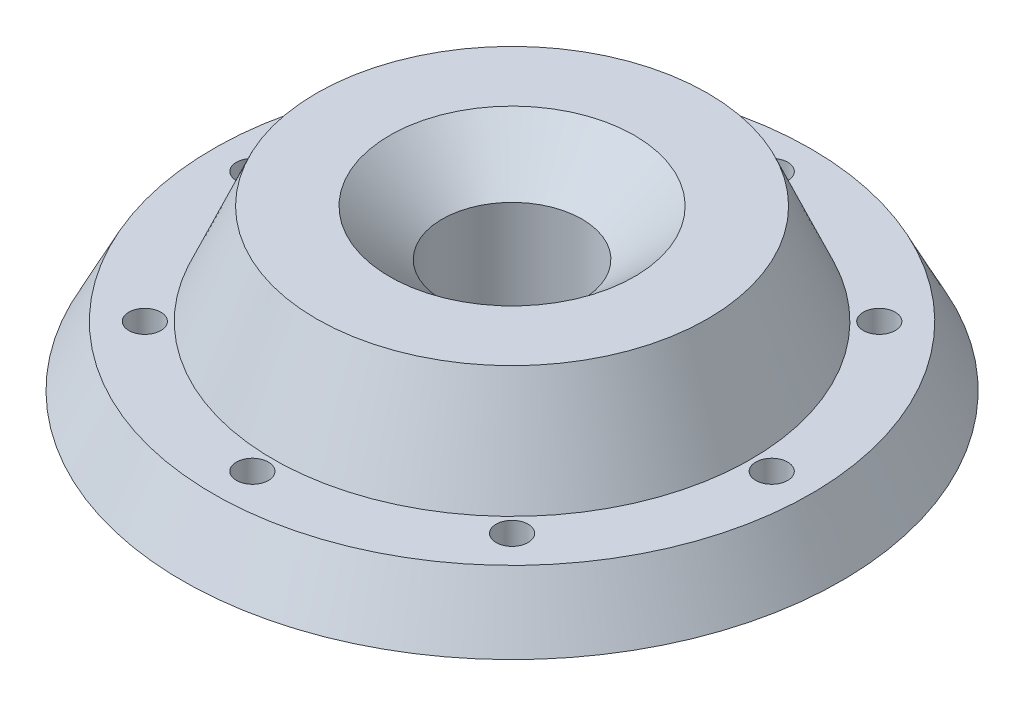
SolidWorks part; units mm, degrees
ref_plane "Front Plane" through (0, 0, 0) normal (0, 0, 1) x (1, 0, 0)
ref_plane "Top Plane" through (0, 0, 0) normal (0, 1, 0) x (1, 0, 0)
ref_plane "Right Plane" through (0, 0, 0) normal (1, 0, 0) x (0, 0, -1)
sketch "Sketch1" plane through (0, 0, 0) normal (0, 1, 0) x (1, 0, 0)
  circle A0 centre (0, 0) radius 56 construction
  circle A1 centre (0, 0) radius 82.5 construction
  circle A2 centre (65, 0) radius 4 construction
  circle A3 centre (65, 0) radius 4
  circle A4 centre (45.9619, -45.9619) radius 4 construction
  circle A5 centre (0, -65) radius 4 construction
  circle A6 centre (-45.9619, -45.9619) radius 4 construction
  circle A7 centre (-65, 0) radius 4 construction
  circle A8 centre (-45.9619, 45.9619) radius 4 construction
  circle A9 centre (0, 65) radius 4 construction
  circle A10 centre (45.9619, 45.9619) radius 4 construction
  circle A11 centre (45.9619, -45.9619) radius 4
  circle A12 centre (0, -65) radius 4
  circle A13 centre (-45.9619, -45.9619) radius 4
  circle A14 centre (-65, 0) radius 4
  circle A15 centre (-45.9619, 45.9619) radius 4
  circle A16 centre (0, 65) radius 4
  circle A17 centre (45.9619, 45.9619) radius 4
  circle A18 centre (0, 0) radius 55 construction
  dimension "D1" = 165
  dimension "D2" = 13.5
  dimension "D3" = 1
sketch "Sketch2" plane through (0, 0, 0) normal (0, 0, 1) x (1, 0, 0)
  line L0 (0, 0) -> (0, 67.5538) construction
  line L1 (82.5, 0) -> (56, 0)
  line L2 (82.5, 0) -> (-82.5, 0) construction
  line L3 (56, 0) -> (-56, 0) construction
  line L4 (56, 0) -> (53.8592, 2.6)
  line L5 (53.8592, 2.6) -> (17.5, 2.6)
  line L6 (17.5, 2.6) -> (17.5, 28.4243)
  line L7 (30.6426, 40) -> (48.9487, 40)
  line L8 (74.8255, 15) -> (82.5, 0)
  line L9 (17.5, 28.4243) -> (30.6426, 40)
  line L10 (74.8255, 15) -> (59.8008, 15)
  line L11 (59.8008, 15) -> (48.9487, 40)
  point P8 (59.8008, 15)
  point P19 (48.9487, 40)
  point P20 (79, 0)
  point P21 (74.8255, 15)
  dimension "D1" = 2.6
  dimension "D2" = 40
  dimension "D3" = 35
  dimension "D4" = 15
revolve "Revolve1" add sketch "Sketch2" angle 360 about L0
sketch "Sketch3" plane through (0, 0, 0) normal (0, -1, 0) x (1, 0, 0)
  circle A1 centre (65, 0) radius 4
  circle A2 centre (65, 0) radius 4
  circle A3 centre (45.9619, -45.9619) radius 4
  circle A4 centre (45.9619, -45.9619) radius 4
  circle A5 centre (0, -65) radius 4
  circle A6 centre (0, -65) radius 4
  circle A7 centre (-45.9619, -45.9619) radius 4
  circle A8 centre (-45.9619, -45.9619) radius 4
  circle A9 centre (-65, 0) radius 4
  circle A10 centre (-65, 0) radius 4
  circle A11 centre (-45.9619, 45.9619) radius 4
  circle A12 centre (-45.9619, 45.9619) radius 4
  circle A13 centre (0, 65) radius 4
  circle A14 centre (0, 65) radius 4
  circle A15 centre (45.9619, 45.9619) radius 4
  circle A16 centre (45.9619, 45.9619) radius 4
  dimension "D1" = 0
  dimension "D2" = 0
  dimension "D3" = 0
  dimension "D4" = 0
  dimension "D5" = 0
  dimension "D6" = 0
  dimension "D7" = 0
  dimension "D8" = 0
extrude "Cut-Extrude2" cut sketch "Sketch3" against normal through all
